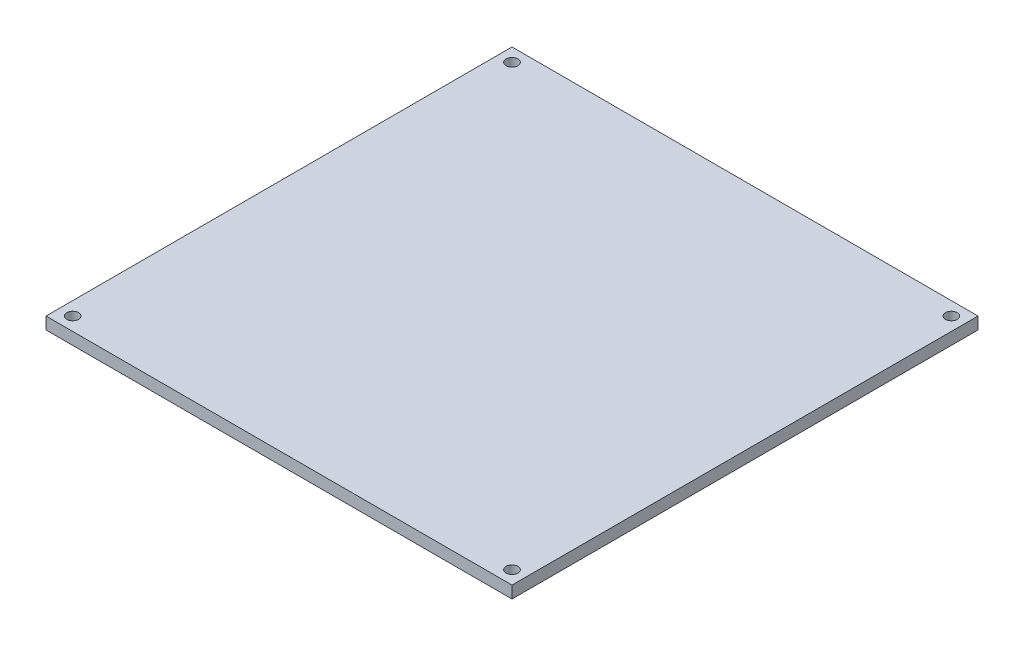
SolidWorks part; units mm, degrees
ref_plane "Front Plane" through (0, 0, 0) normal (0, 0, 1) x (1, 0, 0)
ref_plane "Top Plane" through (0, 0, 0) normal (0, 1, 0) x (1, 0, 0)
ref_plane "Right Plane" through (0, 0, 0) normal (1, 0, 0) x (0, 0, -1)
sketch "Sketch1" plane through (0, 0, 0) normal (0, 1, 0) x (1, 0, 0)
  line L0 (-47.5, 25.0543) -> (29.5, 25.0543) construction
  line L1 (29.5, 25.0543) -> (-9, 63.5543) construction
  line L2 (-9, -13.4457) -> (-9, -21.4272) construction
  line L3 (-47.5, 63.5543) -> (-47.5, -13.4457)
  line L4 (-47.5, 63.5543) -> (29.5, 63.5543)
  line L6 (-47.5, -13.4457) -> (29.5, -13.4457)
  line L7 (29.5, 63.5543) -> (29.5, -13.4457)
  line L13 (-46.0071, 62.0234) -> (-44.631, 60.6472) construction
  line L14 (-9, 63.5543) -> (-9, 25.0543) construction
  circle A2 centre (-45.3, 61.3543) radius 0.9735
  circle A6 centre (27.3, 61.3543) radius 0.9735
  circle A7 centre (-45.3, -11.2457) radius 0.9735
  circle A8 centre (27.3, -11.2457) radius 0.9735
  point P21 (-47.5, 61.9915)
  dimension "D3" = 2.2
  dimension "D1" = 77
  dimension "D2" = 38.5
  dimension "D4" = 2.2
extrude "Boss-Extrude1" add sketch "Sketch1" along normal blind 2
